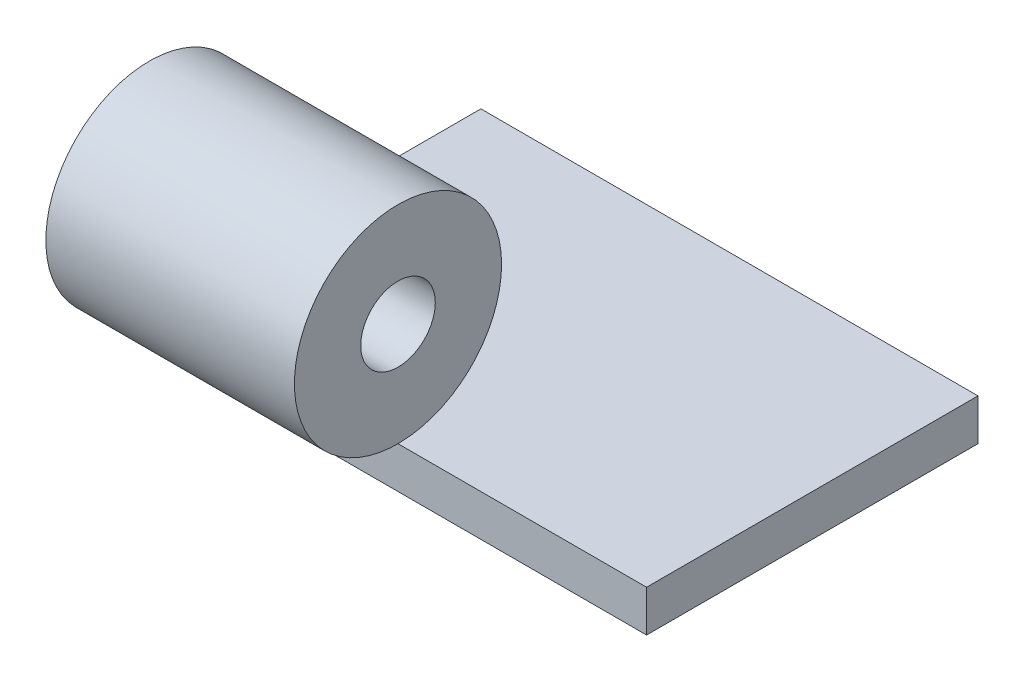
SolidWorks part; units mm, degrees
material "AISI 316 Отожженная нержавеющая сталь. полоса (SS)"
ref_plane "Спереди (XY)" through (0, 0, 0) normal (0, 0, 1) x (1, 0, 0)
ref_plane "Сверху (XZ)" through (0, 0, 0) normal (0, 1, 0) x (1, 0, 0)
ref_plane "Справа (ZY)" through (0, 0, 0) normal (1, 0, 0) x (0, 0, -1)
sketch "Эскиз4" plane through (0, 0, 0) normal (1, 0, 0) x (0, 0, -1)
  line L1 (20, -5) -> (-20, -5)
  line L2 (20, -5) -> (20, 0)
  line L3 (20, 0) -> (-20, 0)
  line L4 (-20, -5) -> (-20, 0)
  line L5 (20, -5) -> (-20, 0) construction
  line L6 (20, 0) -> (-20, -5) construction
  point P0 (0, -2.5)
  dimension "D1" = 5
  dimension "D2" = 40
extrude "Бобышка-Вытянуть5" add sketch "Эскиз4" along normal mid plane 60
sketch "Эскиз9" plane through (0, 0, 0) normal (1, 0, 0) x (0, 0, -1)
  line L0 (20, 0) -> (-20, 0) construction
  line L1 (20, 0) -> (-20, 0) construction
  line L2 (-20, -20.5076) -> (-20, 24.2716) construction
  circle A0 centre (-20, 12.5) radius 12.5
  dimension "D1" = 25
extrude "Вытянуть-Тонкостенный8" add sketch "Эскиз9" against normal blind 30 separate body thin thin type one direction reverse wall 8
extrude "Бобышка-Вытянуть10" add sketch "Эскиз9<2>" along normal blind 5 from vertex starting at point (-30, 0, -20)
sketch "Эскиз9<2>" plane through (0, 0, 0) normal (1, 0, 0) x (0, 0, -1) same geometry as "Эскиз9"
